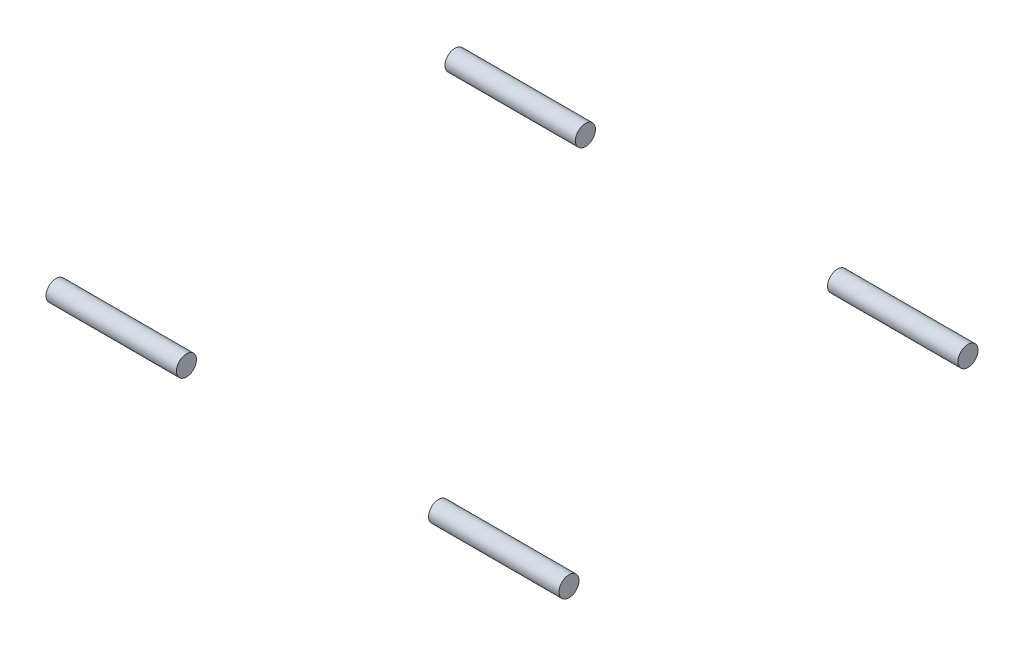
SolidWorks part; units mm, degrees
material "6061-T6 (SS)"
ref_plane "Front Plane" through (0, 0, 0) normal (0, 0, 1) x (1, 0, 0)
ref_plane "Top Plane" through (0, 0, 0) normal (0, 1, 0) x (1, 0, 0)
ref_plane "Right Plane" through (0, 0, 0) normal (1, 0, 0) x (0, 0, -1)
sketch "Sketch1" plane through (81.165, 0, 0) normal (-1, 0, 0) x (0, 0, 1)
  circle A0 centre (126.25, 0) radius 3.175
  circle A1 centre (0, 0) radius 3.175
  circle A2 centre (0, 0) radius 3.175 construction
  circle A3 centre (126.25, 0) radius 3.175 construction
extrude "Boss-Extrude1" add sketch "Sketch1" along normal blind 41.275
mirror "Mirror1" about plane through (0, 0, 0) normal (1, 0, 0) of bodies 101 102
